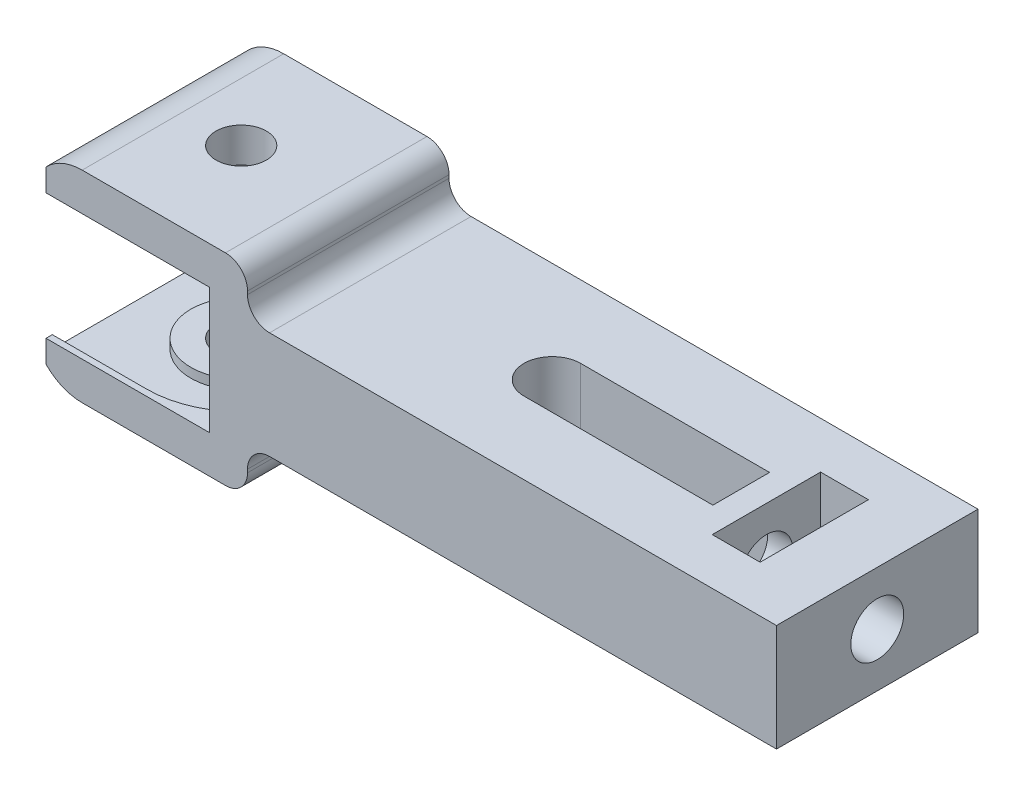
SolidWorks part; units mm, degrees
ref_plane "Front Plane" through (0, 0, 0) normal (0, 0, 1) x (1, 0, 0)
ref_plane "Top Plane" through (0, 0, 0) normal (0, 1, 0) x (1, 0, 0)
ref_plane "Right Plane" through (0, 0, 0) normal (1, 0, 0) x (0, 0, -1)
sketch "Sketch1" plane through (0, 0, 0) normal (0, 0, 1) x (1, 0, 0)
  line L0 (0, 0) -> (-42, 0)
  line L1 (-42, 0) -> (-42, 3.75)
  line L2 (-42, 3.75) -> (-59, 3.75)
  line L3 (-59, 3.75) -> (-59, 0.75)
  line L4 (-59, 0.75) -> (-45, 0.75)
  line L5 (-45, 0.75) -> (-45, -9.25)
  line L6 (0, 0) -> (0, -8.5)
  line L7 (0, -4.25) -> (-45, -4.25) construction
  line L8 (-59, -9.25) -> (-45, -9.25)
  line L9 (-59, -12.25) -> (-59, -9.25)
  line L10 (-42, -12.25) -> (-59, -12.25)
  line L11 (-42, -8.5) -> (-42, -12.25)
  line L12 (0, -8.5) -> (-42, -8.5)
  dimension "D1" = 59
  dimension "D2" = 14
  dimension "D3" = 4.25
  dimension "D4" = 5
  dimension "D5" = 3
  dimension "D6" = 17
extrude "Boss-Extrude1" add sketch "Sketch1" along normal blind 16
sketch "Sketch2" plane through (0, 0, 0) normal (0, 1, 0) x (1, 0, 0)
  line L0 (0, -8) -> (-42, -8) construction
  line L1 (0, -16) -> (0, 0) construction
  line L2 (-42, -16) -> (-42, 0) construction
  line L4 (-8.8, -3.7) -> (-5, -3.7)
  line L5 (-8.8, -3.7) -> (-8.8, -12.3)
  line L6 (-8.8, -12.3) -> (-5, -12.3)
  line L7 (-5, -3.7) -> (-5, -12.3)
  line L8 (-8.8, -3.7) -> (-5, -12.3) construction
  line L9 (-8.8, -12.3) -> (-5, -3.7) construction
  line L10 (-25.8, -10.25) -> (-10.8, -10.25)
  line L12 (-25.8, -5.75) -> (-10.8, -5.75)
  line L13 (-10.8, -10.25) -> (-10.8, -5.75)
  line L14 (-25.8, -10.25) -> (-10.8, -5.75) construction
  line L15 (-25.8, -5.75) -> (-10.8, -10.25) construction
  arc A0 (-25.8, -5.75) -> (-25.8, -10.25) centre (-25.8, -8) ccw
  point P6 (-6.9, -8)
  point P11 (-18.3, -8)
  dimension "D7" = 2.25
  dimension "D1" = 8.6
  dimension "D2" = 3.8
  dimension "D3" = 5
  dimension "D4" = 2
  dimension "D5" = 4.5
  dimension "D6" = 15
extrude "Cut-Extrude1" cut sketch "Sketch2" against normal through all
sketch "Sketch3" plane through (0, 0, 0) normal (1, 0, 0) x (0, 0, -1)
  line L0 (-8, 0) -> (-8, -8.5) construction
  line L1 (-16, 0) -> (0, 0) construction
  line L2 (-16, -8.5) -> (0, -8.5) construction
  circle A0 centre (-8, -4.25) radius 2.1
  dimension "D1" = 4.2
extrude "Cut-Extrude2" cut sketch "Sketch3" against normal up to surface (10.8 mm away) up to face at (-10.8, -4.25, 8)
fillet "Fillet1" radius 1.75 4 edges at (-42, -8.5, 8) (-42, 3.75, 8) (-42, 0, 8) (-42, -12.25, 8)
sketch "Sketch4" plane through (0, -9.25, 0) normal (0, 1, 0) x (1, 0, 0)
  line L0 (-59, -8) -> (-43.75, -8) construction
  line L1 (-59, -16) -> (-59, 0) construction
  line L2 (-43.75, 0) -> (-43.75, -16) construction
  circle A0 centre (-51.375, -8) radius 9
  dimension "D1" = 18
extrude "Cut-Extrude3" cut sketch "Sketch4" along normal up to surface (10 mm away) up to face at (-52, 0.75, 8)
sketch "Sketch5" plane through (0, 3.75, 0) normal (0, 1, 0) x (1, 0, 0)
  line L0 (-59, -8) -> (-43.75, -8) construction
  line L1 (-59, -16) -> (-59, 0) construction
  line L2 (-43.75, -16) -> (-43.75, 0) construction
  circle A0 centre (-50.5, -8) radius 2
  dimension "D1" = 4
  dimension "D2" = 8.5
extrude "Cut-Extrude4" cut sketch "Sketch5" against normal through all
fillet "Fillet2" radius 4 2 edges at (-59, -12.25, 8) (-59, 3.75, 8)
sketch "Sketch6" plane through (0, -9.25, 0) normal (0, 1, 0) x (1, 0, 0)
  line L0 (-50.5, -0.5) -> (-59, -0.5)
  line L1 (-59, -16) -> (-59, 0) construction
  line L2 (-50.5, -15.5) -> (-59, -15.5)
  line L3 (-59, -15.5) -> (-59, -0.5)
  arc A0 (-50.5, -15.5) -> (-50.5, -0.5) centre (-50.5, -8) ccw
  dimension "D1" = 15
extrude "Cut-Extrude5" cut sketch "Sketch6" against normal blind 1
sketch "Sketch7" plane through (0, -10.25, 0) normal (0, 1, 0) x (1, 0, 0)
  circle A0 centre (-50.5, -8) radius 4
  circle A1 centre (-50.5, -8) radius 2
  circle A2 centre (-50.5, -8) radius 2 construction
  dimension "D1" = 8
extrude "Boss-Extrude2" add sketch "Sketch7" along normal blind 0.75
ref_plane "Plane1" through (0, -4.25, 0) normal (0, 1, 0) x (1, 0, 0)
mirror "Mirror1" about plane through (0, -4.25, 0) normal (0, 1, 0) of "Boss-Extrude2", "Cut-Extrude5"
sketch "Sketch8" plane through (0, 0, 16) normal (0, 0, 1) x (1, 0, 0)
  line L0 (0, -4.25) -> (-60, -4.25) construction
  line L1 (0, -8.5) -> (0, 0) construction
  line L2 (8.8, -4.25) -> (-8.8, -4.25) construction
  line L3 (-43.75, 3.75) -> (-55.127, 3.75) construction
  line L4 (-62, -12.25) -> (-58, -12.25)
  line L5 (-62, -12.25) -> (-62, 3.75)
  line L6 (-62, 3.75) -> (-58, 3.75)
  line L7 (-58, -12.25) -> (-58, 3.75)
  line L8 (-62, -12.25) -> (-58, 3.75) construction
  line L9 (-62, 3.75) -> (-58, -12.25) construction
  dimension "D1" = 1
  dimension "D2" = 2
extrude "Cut-Extrude6" cut sketch "Sketch8" against normal through all
equation "\"X-ROD-SPACING\"=45"
equation "\"Y-ROD-SPACING\"=75"
equation "\"Z-ROD-SPACING\"=17.5"
equation "\"Y-BED-OFFSET\"=2"
equation "\"Y-BED-ROD-INSET\"=3.5"
equation "\"T-SLOT-NUT-FILLET-RADIUS\"=0.5"
equation "\"T-SLOT-SCREW-SHAFT-RADIUS\"=1.55"
equation "\"T-SLOT-SCREW-SHAFT-CUTOUT-LENGTH\"=11"
equation "\"T-SLOT-NUT-DEPTH\"=3.5"
equation "\"T-SLOT-NUT-WIDTH\"=2.85"
equation "\"T-SLOT-NUT-END-DISTANCE\"=8"
equation "\"ACRYLIC-THICKNESS\"=10"
equation "\"ACRYLIC-TAB-CUTOUT-SIZE\"=\"ACRYLIC-THICKNESS\"+\"ACRYLIC-TAB-TOLERANCE\"*2"
equation "\"ACRYLIC-TAB-WIDTH\"=\"ACRYLIC-THICKNESS\""
equation "\"ACRYLIC-M3-HOLE\"=2.9"
equation "\"SMOOTHROD-CAP-SCREW-DISTANCE\"=20"
equation "\"FRAME-WIDTH-INNER\"=370"
equation "\"NEMA17-HOLE-SPACING\"=31"
equation "\"NEMA17-CENTRAL-CUTOUT\"=22.5"
equation "\"Z-BRACKET-REACH\"=57"
equation "\"TOP-BRACKET-SPACING\"=40"
equation "\"SMOOTHROD-X-LENGTH\"=350"
equation "\"SMOOTHROD-Y-LENGTH\"=350"
equation "\"SMOOTHROD-Z-LENGTH\"=350"
equation "\"SMOOTHROD-TIGHTENING-HEADROOM\"=.25"
equation "\"LEADSCREW-Z-LENGTH\"=300"
equation "\"SCREW-HEAD-RADIUS\"=6"
equation "\"PRINTED-X-SMOOTHROD-DIAMETER\"=8.8"
equation "\"PRINTED-X-SMOOTHROD-CUTOUT\"=10"
equation "\"PRINTED-X-BASE-HEIGHT\"=10"
equation "\"PRINTED-LM8UU-CUTOUT-SIZE\"=15.5"
equation "\"PRINTED-LM8UU-CUTOUT-LENGTH\"=24.5"
equation "\"PRINTED-X-IDLER-HEIGHT\"=16"
equation "\"D1@Boss-Extrude1\"=\"PRINTED-X-IDLER-HEIGHT\""
